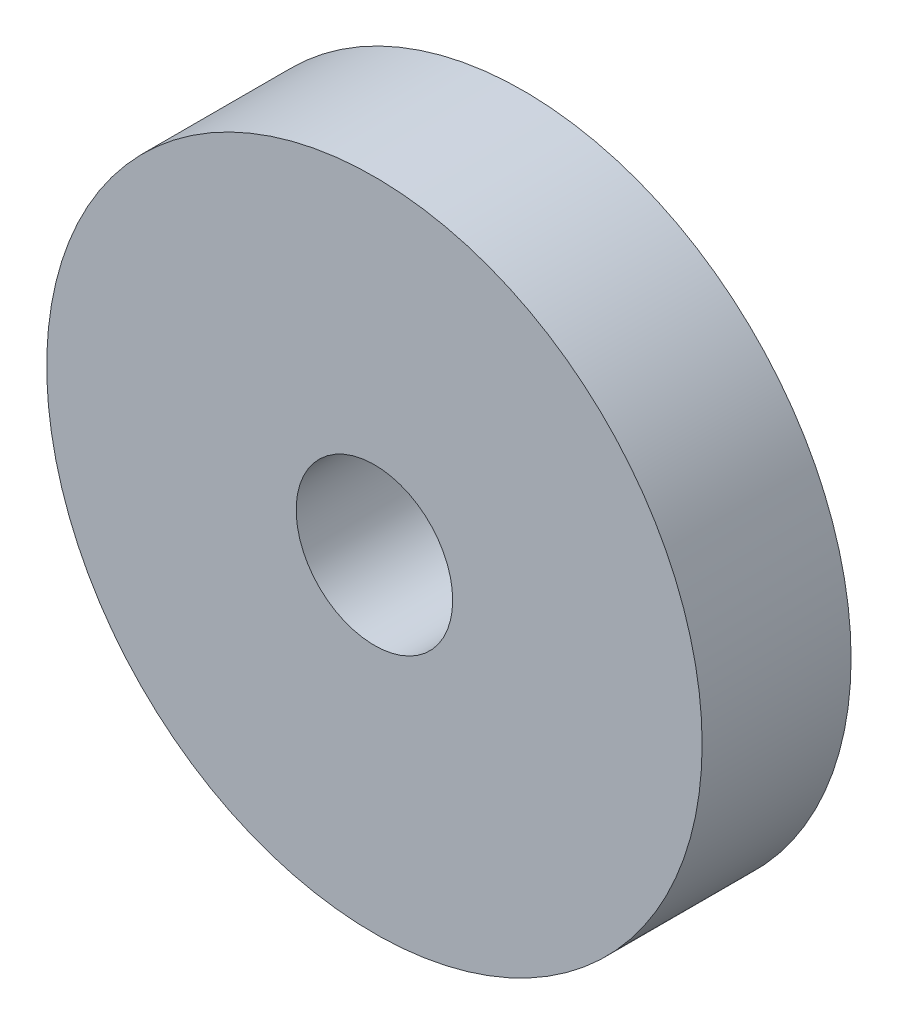
SolidWorks part; units mm, degrees
ref_plane "Front Plane" through (0, 0, 0) normal (0, 0, 1) x (1, 0, 0)
ref_plane "Top Plane" through (0, 0, 0) normal (0, 1, 0) x (1, 0, 0)
ref_plane "Right Plane" through (0, 0, 0) normal (1, 0, 0) x (0, 0, -1)
sketch "Sketch2" plane through (0, 0, 0) normal (0, 0, 1) x (1, 0, 0)
  circle A0 centre (0, 0) radius 11
  dimension "D1" = 22
extrude "Boss-Extrude1" add sketch "Sketch2" along normal blind 5
sketch "Sketch3" plane through (0, 0, 5) normal (0, 0, 1) x (1, 0, 0)
  circle A0 centre (0, 0) radius 2.627
  dimension "D1" = 5.254
extrude "Cut-Extrude1" cut sketch "Sketch3" against normal blind 5
equation "\"D1@Sketch3\"=5mm+0.01in"
